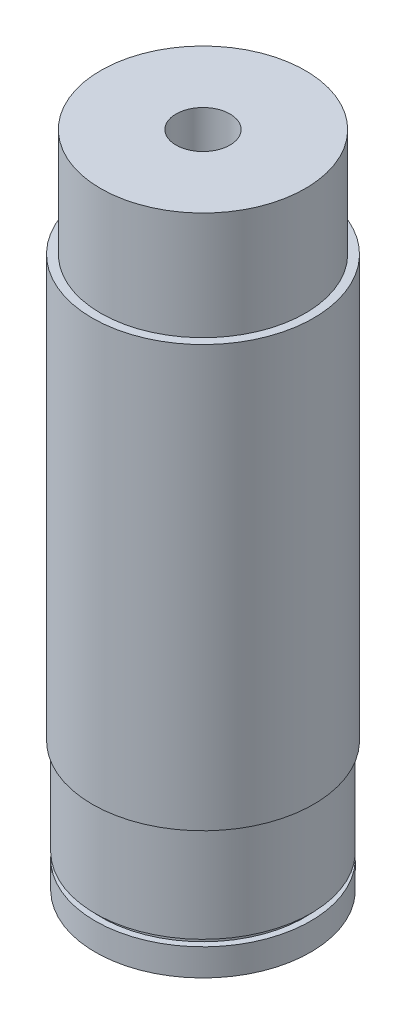
SolidWorks part; units mm, degrees
material "ABS"
ref_plane "Plan de face" through (0, 0, 0) normal (0, 0, 1) x (1, 0, 0)
ref_plane "Plan de dessus" through (0, 0, 0) normal (0, 1, 0) x (1, 0, 0)
ref_plane "Plan de droite" through (0, 0, 0) normal (1, 0, 0) x (0, 0, -1)
sketch "Esquisse1" plane through (0, 0, 0) normal (0, 1, 0) x (1, 0, 0)
  circle A0 centre (0, 0) radius 20.5
  dimension "D1" = 41
extrude "Boss.-Extru.1" add sketch "Esquisse1" along normal blind 122
sketch "Esquisse2" plane through (0, 122, 0) normal (0, 1, 0) x (1, 0, 0)
  circle A0 centre (0, 0) radius 18.95
  dimension "D1" = 37.9
extrude "Enlèv. mat.-Extru.1" cut sketch "Esquisse2" against normal blind 20 flip side to cut
sketch "Esquisse3" plane through (0, 0, 0) normal (0, -1, 0) x (1, 0, 0)
  circle A0 centre (0, 0) radius 19.95
  dimension "D1" = 39.9
extrude "Enlèv. mat.-Extru.2" cut sketch "Esquisse3" against normal blind 24 flip side to cut
sketch "Esquisse4" plane through (0, 0, 0) normal (0, 0, 1) x (1, 0, 0)
  line L0 (-19.95, 24) -> (-19.95, 0) construction
  line L1 (-21.1, 6.2) -> (-18.8, 6.2)
  line L2 (-21.1, 6.2) -> (-21.1, 5)
  line L3 (-21.1, 5) -> (-18.8, 5)
  line L4 (-18.8, 6.2) -> (-18.8, 5)
  line L5 (-21.1, 6.2) -> (-18.8, 5) construction
  line L6 (-21.1, 5) -> (-18.8, 6.2) construction
  line L7 (-19.95, 0) -> (19.95, 0) construction
  line L8 (0, 0) -> (0, 8.7803) construction
  point P0 (-19.95, 5.6)
  dimension "D1" = 1.2
  dimension "D2" = 18.8
  dimension "D3" = 5
revolve "Enlèvement de matière-Révolution1" cut sketch "Esquisse4" angle 360 about L8
sketch "Esquisse5" plane through (0, 122, 0) normal (0, 1, 0) x (1, 0, 0)
  circle A0 centre (0, 0) radius 5
  dimension "D1" = 10
extrude "Enlèv. mat.-Extru.3" cut sketch "Esquisse5" against normal through all
